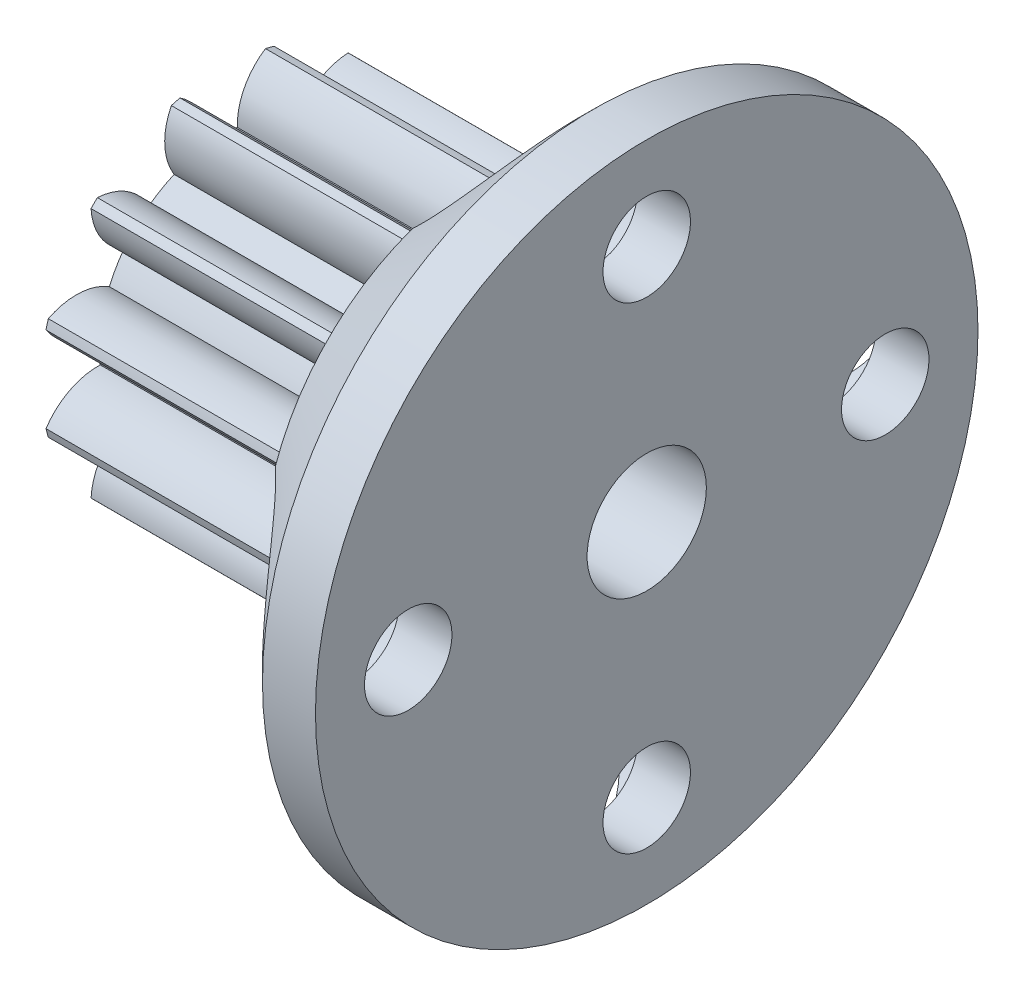
SolidWorks part; units mm, degrees
ref_plane "Plane1" through (0, 0, 0) normal (0, 0, 1) x (1, 0, 0)
ref_plane "Plane2" through (0, 0, 0) normal (0, 1, 0) x (1, 0, 0)
ref_plane "Plane3" through (0, 0, 0) normal (1, 0, 0) x (0, 0, -1)
other "Configuration Table"
sketch "HoldingSke" plane through (0, 0, 0) normal (0, 1, 0) x (1, 0, 0)
  line L0 (0, 0) -> (0.9981, -0.2122)
  line L1 (-15, 0) -> (100, 0) construction
  line L2 (0, 0) -> (-2.1039, 2.3779)
  line L3 (0, 0) -> (-11.863, 4.5341)
  line L4 (0, 0) -> (8.4473, 1.7955)
  line L5 (0, 0) -> (-46.8476, -17.4728)
  line L6 (0, 0) -> (-8.2896, -5.593)
  line L7 (-2.1039, 2.3779) -> (8.6586, 51.2059)
  line L8 (-76.2, 54.61) -> (-75.5, 54.61)
  line L9 (-71.009, 38.7566) -> (-53.1078, 45.2721)
  line L10 (-76.2, 71.12) -> (104.1128, 71.12)
  line L11 (0, 0) -> (-10, 0)
  line L12 (-76.2, 101.6) -> (-76.162, 101.6)
  line L13 (24.9733, 27.94) -> (52.9518, 28.4284)
  line L14 (24.9733, 27.94) -> (24.9743, 27.94)
  line L15 (24.9733, 27.94) -> (100.4006, 29.5858)
  line L16 (-63.627, -0.98) -> (-12.827, -0.98)
  circle A0 centre (0, 0) radius 1
  circle A1 centre (0, 0) radius 4.654
  circle A2 centre (0, 0) radius 37.5
  circle A3 centre (0, 0) radius 1
  dimension "Num_teeth" = 12
  dimension "Pitch_radius" = 180.3128
  dimension "Width" = 10
  dimension "Thickness" = 10
sketch "BasProSke" plane through (0, 0, 0) normal (0, 1, 0) x (1, 0, 0)
  line L0 (-10, 0) -> (60, 0) construction
  line L1 (0, 0) -> (0, 6.86)
  line L2 (0, 0) -> (10, 0)
  line L3 (10, 0) -> (10, 6.86)
  line L4 (10, 6.86) -> (0, 6.86)
  dimension "Thickness" = 10
  dimension "Diameter" = 13.72
revolve "Base-Revolve" add sketch "BasProSke" angle 360 about L0
sketch "TooCutSke" plane through (0, 0, 0) normal (1, 0, 0) x (0, 0, -1)
  line L1 (0, 0) -> (0, 107) construction
  line L2 (0, 0) -> (-0.8339, 5.8206) construction
  line L3 (0, 0) -> (-3.022, 11.2783) construction
  line L4 (-0.8339, 5.8206) -> (-1.511, 5.6391) construction
  arc A0 (0.552, 4.6211) -> (-0.552, 4.6211) centre (0, 0) ccw
  arc A1 (1.6415, 6.6869) -> (-1.6415, 6.6869) centre (0, 0) ccw
  circle A2 centre (0, 0) radius 5.88 construction
  circle A3 centre (0, 0) radius 5.5254 construction
  arc A4 (-0.552, 4.6211) -> (-1.6415, 6.6869) centre (-2.9026, 4.7016) ccw
  arc A5 (1.6415, 6.6869) -> (0.552, 4.6211) centre (2.9026, 4.7016) ccw
extrude "ToothCut" cut sketch "TooCutSke" along normal through all
fillet "Breaks" [suppressed] radius 0.0196 tangent propagation no
fillet "RootFillets" [suppressed] radius 0.246
pattern_circular "TeethCuts" count 12 every 30 about axis through (-10, 0, 0) along (1, 0, 0) of "ToothCut", "RootFillets", "Breaks"
sketch "HubNeaOneSke" plane through (0, 0, 0) normal (-1, 0, 0) x (0, 0, 1)
  circle A0 centre (0, 0) radius 4.654
  dimension "Diameter" = 9.308
extrude "HubNearOne" [suppressed] add sketch "HubNeaOneSke" along normal blind 40.0001
sketch "HubNeaBotSke" plane through (0, 0, 0) normal (-1, 0, 0) x (0, 0, 1)
  circle A0 centre (0, 0) radius 4.654
  dimension "Diameter" = 9.308
extrude "HubNearBoth" [suppressed] add sketch "HubNeaBotSke" along normal blind 20
ref_plane "FarPln" through (10, 0, 0) normal (1, 0, 0) x (0, 0, -1)
sketch "HubFarSke" plane through (10, 0, 0) normal (1, 0, 0) x (0, 0, -1)
  circle A0 centre (0, 0) radius 4.654
  dimension "Diameter" = 9.308
extrude "HubFar" [suppressed] add sketch "HubFarSke" along normal blind 20
sketch "BorSke" plane through (0, 0, 0) normal (1, 0, 0) x (0, 0, -1)
  circle A0 centre (0, 0) radius 1
  dimension "Diameter" = 2
extrude "Bore" cut sketch "BorSke" along normal mid plane 100.0001
sketch "KeySke" plane through (0, 0, 0) normal (1, 0, 0) x (0, 0, -1)
  line L0 (-0.8, 0) -> (-0.8, 1.7)
  line L1 (-0.8, 1.7) -> (0.8, 1.7)
  line L2 (0.8, 1.7) -> (0.8, 0)
  line L3 (0, 0) -> (0, 34) construction
  line L4 (-0.8, 0) -> (0.8, 0)
  dimension "Width" = 1.6
extrude "Keyway" [suppressed] cut sketch "KeySke" along normal mid plane 100.0001
pattern_circular "Keyway2" [suppressed] count 2 every 90 about axis through (-10, 0, 0) along (1, 0, 0) reverse direction yes
sketch "Sketch1" plane through (10, 0, 0) normal (1, 0, 0) x (0, 0, -1)
  circle A0 centre (0, 0) radius 12.5
  dimension "D1" = 25
extrude "Boss-Extrude1" add sketch "Sketch1" along normal blind 6
sketch "Sketch2" plane through (10, 0, 0) normal (-1, 0, 0) x (0, 0, 1)
  circle A0 centre (0, 9) radius 1.65
  point P2 (0, 0)
  dimension "D1" = 3.3
  dimension "D2" = 9
extrude "Cut-Extrude1" cut sketch "Sketch2" against normal through all
sketch "Sketch3" plane through (10, 0, 0) normal (-1, 0, 0) x (0, 0, 1)
  circle A0 centre (0, 9) radius 3
  dimension "D1" = 6
extrude "Cut-Extrude2" cut sketch "Sketch3" against normal blind 4
pattern_circular "CirPattern1" count 4 over 360 about axis through (16, 0, 0) along (-1, 0, 0) of "Cut-Extrude1", "Cut-Extrude2" reverse direction yes
chamfer "Chamfer1" distance 4 angle 45 1 edges at (10, 0, -12.5)
sketch "Sketch4" plane through (16, 0, 0) normal (1, 0, 0) x (0, 0, -1)
  circle A0 centre (0, 0) radius 2.25
  dimension "D1" = 4.5
extrude "Cut-Extrude3" cut sketch "Sketch4" against normal blind 6
equation "' \"Module@HoldingSke\" = 6.35"
equation "' \"Num_teeth@HoldingSke\" = 12"
equation "' \"Ap@HoldingSke\" =  20"
equation "' \"Ap@HoldingSke\" = 20"
equation "' \"Width@HoldingSke\" = 0.5 * 25.4"
equation "' \"Hub_dia@HoldingSke\"= 1 * 25.4"
equation "' \"Hub_dia@HoldingSke\" = 1 * 25.4"
equation "' \"Overall_len@HoldingSke\" = 1.0 * 25.4"
equation "' \"Bore@HoldingSke\" = 0.75 * 25.4"
equation "' \"T_dim@HoldingSke\" = 0.1 * 25.4"
equation "' \"Width@KeySke\" = 0.25 * 25.4"
equation "' \"Show_teeth@HoldingSke\" = 13"
equation "' \"Backlash@HoldingSke\" = 0.009 * 25.4"
equation "' \"Addendum_fac@HoldingSke\" = 1.0"
equation "' \"Dedendum_fac@HoldingSke\" = 1.25"
equation "' \"Dedendum_add@HoldingSke\" = 0.00005 * 25.4"
equation "' \"Clearance_fac@HoldingSke\" = 0.25"
equation "\"Pitch@HoldingSke\" = 1 / \"Module@HoldingSke\""
equation "\"Overcut_dia@TooCutSke\" = (\"Num_teeth@HoldingSke\" + 2 * \"Addendum_fac@HoldingSke\") / \"Pitch@HoldingSke\" + 0.002 * 25.4"
equation "\"Pitch_dia@TooCutSke\" = \"Num_teeth@HoldingSke\" / \"Pitch@HoldingSke\""
equation "\"Base_dia@TooCutSke\" = \"Num_teeth@HoldingSke\" / \"Pitch@HoldingSke\" * cos((\"Ap@HoldingSke\"  * 3.14159265 / 180))"
equation "\"Root_dia@TooCutSke\" = (\"Num_teeth@HoldingSke\" + 2) / \"Pitch@HoldingSke\" - 2 * (\"Addendum_fac@HoldingSke\" + \"Dedendum_fac@HoldingSke\") / \"Pitch@HoldingSke\" - \"Dedendum_add@HoldingSke\" * 2"
equation "\"Half_ang@TooCutSke\" = 180 / \"Num_teeth@HoldingSke\""
equation "\"Half_CT@TooCutSke\" = \"Num_teeth@HoldingSke\" / \"Pitch@HoldingSke\" * sin((3.14159265 / 2 / \"Num_teeth@HoldingSke\")) / 2 - 7 * \"Backlash@HoldingSke\" / 4"
equation "\"Flank_rad@TooCutSke\" = \"Num_teeth@HoldingSke\" / \"Pitch@HoldingSke\" / 5"
equation "\"Radius@RootFillets\" = \"Clearance_fac@HoldingSke\" / \"Pitch@HoldingSke\" + \"Dedendum_add@HoldingSke\""
equation "\"Break_rad@Breaks\" = 0.02 / \"Pitch@HoldingSke\""
equation "\"Thickness@HoldingSke\" = \"Width@HoldingSke\""
equation "\"OAL@HoldingSke\" = \"Thickness@HoldingSke\""
equation "\"MHD@HoldingSke\" = (\"Num_teeth@HoldingSke\" + 2) / \"Pitch@HoldingSke\" - 2 * (\"Addendum_fac@HoldingSke\" + \"Dedendum_fac@HoldingSke\")  / \"Pitch@HoldingSke\" - \"Dedendum_add@HoldingSke\" * 2"
equation "\"MBD@HoldingSke\" = (\"Num_teeth@HoldingSke\" + 2) / \"Pitch@HoldingSke\" - 2 * (\"Addendum_fac@HoldingSke\" + \"Dedendum_fac@HoldingSke\")  / \"Pitch@HoldingSke\" - \"Dedendum_add@HoldingSke\" * 2 - 0.002 * 25.4"
equation "\"MHD@HoldingSke\" = ((sgn( \"MHD@HoldingSke\" - \"Hub_dia@HoldingSke\" )-1)*( \"MHD@HoldingSke\" - \"Hub_dia@HoldingSke\" ))/-2+ \"Hub_dia@HoldingSke\""
equation "\"MBD@HoldingSke\" = ((sgn( \"MBD@HoldingSke\" - \"Bore@HoldingSke\" )-1)*( \"MBD@HoldingSke\" - \"Bore@HoldingSke\" ))/-2+ \"Bore@HoldingSke\""
equation "\"OAL@HoldingSke\" = ((sgn( \"OAL@HoldingSke\" - \"Overall_len@HoldingSke\" )+1)*( \"OAL@HoldingSke\" - \"Overall_len@HoldingSke\" ))/2 + \"Overall_len@HoldingSke\" + 0.000002 * 25.4"
equation "\"Num_teeth@TeethCuts\" = int( \"Show_teeth@HoldingSke\" ) + 1"
equation "\"Num_teeth@TeethCuts\" = ((sgn( \"Num_teeth@TeethCuts\" - \"Num_teeth@HoldingSke\" )-1)*( \"Num_teeth@TeethCuts\" - \"Num_teeth@HoldingSke\" ))/-2+ \"Num_teeth@HoldingSke\""
equation "\"Num_teeth@TeethCuts\" = ((sgn( \"Num_teeth@TeethCuts\" - 2.0)+1)*( \"Num_teeth@TeethCuts\" - 2.0))/2 +2.0"
equation "\"Angle@TeethCuts\" = 360.0 / \"Num_teeth@HoldingSke\""
equation "\"Diameter@BasProSke\" = (\"Num_teeth@HoldingSke\" + 2 * \"Addendum_fac@HoldingSke\") / \"Pitch@HoldingSke\""
equation "\"Thickness@BasProSke\"  = \"Thickness@HoldingSke\""
equation "' \"Fillet_rad@BasProSke\" =  \"Thickness@HoldingSke\" * 0.05"
equation "' \"Fillet_rad@BasProSke\" = \"Thickness@HoldingSke\" * 0.05"
equation "\"MHD@HoldingSke\" = ((sgn( \"MHD@HoldingSke\" - \"Root_dia@TooCutSke\" )-1)*( \"MHD@HoldingSke\" - \"Root_dia@TooCutSke\" ))/-2+ \"Root_dia@TooCutSke\""
equation "\"Diameter@HubNeaOneSke\" = \"MHD@HoldingSke\""
equation "\"Length@HubNearOne\" = \"OAL@HoldingSke\" - \"Thickness@BasProSke\""
equation "\"Diameter@HubNeaBotSke\" = \"MHD@HoldingSke\""
equation "\"Length@HubNearBoth\" = ( \"OAL@HoldingSke\" - \"Thickness@BasProSke\" ) / 2.0"
equation "\"Thickness@FarPln\" = \"Thickness@BasProSke\""
equation "\"Diameter@HubFarSke\" = \"MHD@HoldingSke\""
equation "\"Length@HubFar\" = ( \"OAL@HoldingSke\" - \"Thickness@BasProSke\" ) / 2.0"
equation "\"Diameter@BorSke\" = \"MBD@HoldingSke\""
equation "\"D1@Bore\" = \"OAL@HoldingSke\" * 2.0"
equation "\"D1@Keyway\" = \"OAL@HoldingSke\" * 2.0"
equation "\"Offset@KeySke\" = \"T_dim@HoldingSke\" + \"MBD@HoldingSke\" / 2.0"
